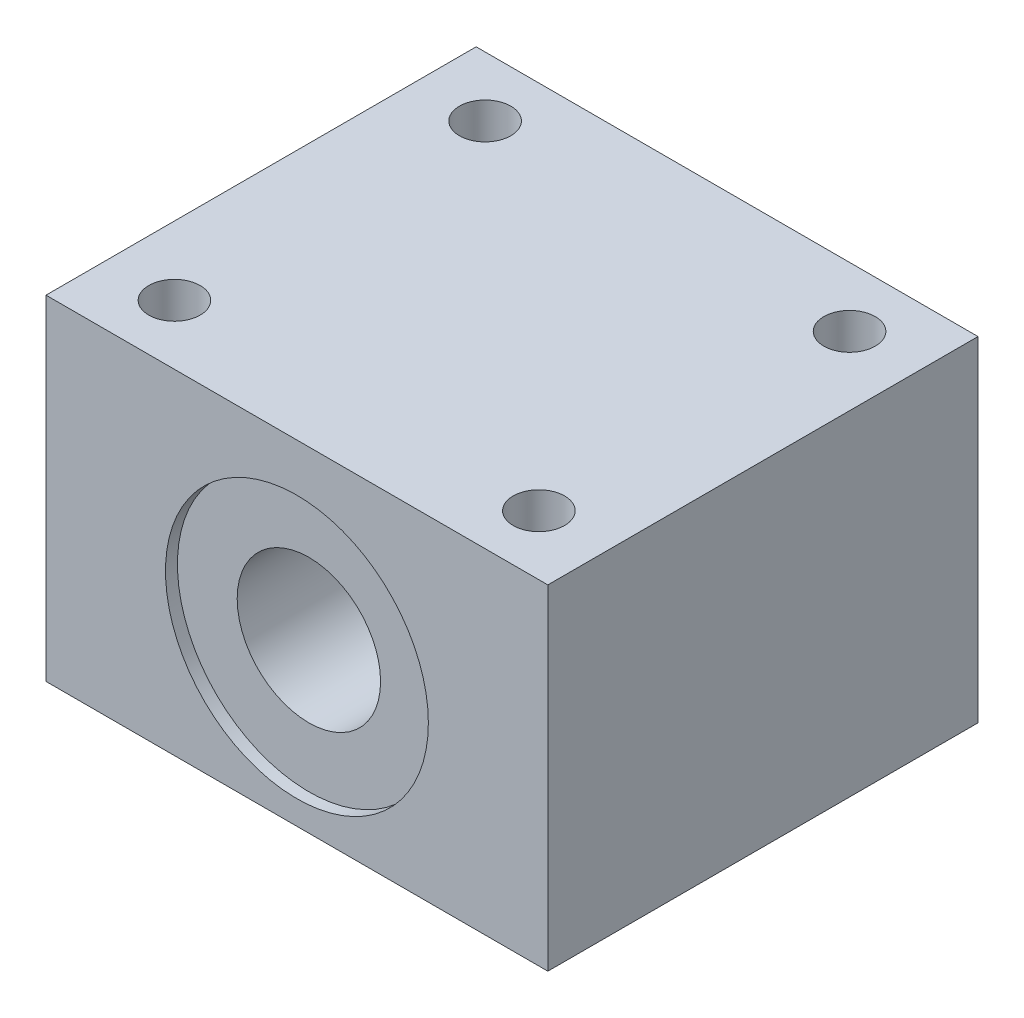
SolidWorks part; units mm, degrees
ref_plane "Front Plane" through (0, 0, 0) normal (0, 0, 1) x (1, 0, 0)
ref_plane "Top Plane" through (0, 0, 0) normal (0, 1, 0) x (1, 0, 0)
ref_plane "Right Plane" through (0, 0, 0) normal (1, 0, 0) x (0, 0, -1)
sketch "Sketch1" plane through (0, 0, 0) normal (0, 0, 1) x (1, 0, 0)
  line L1 (-21, -14) -> (21, -14)
  line L2 (-21, -14) -> (-21, 14)
  line L3 (-21, 14) -> (21, 14)
  line L4 (21, -14) -> (21, 14)
  line L5 (-21, -14) -> (21, 14) construction
  line L6 (-21, 14) -> (21, -14) construction
  circle A0 centre (0, -1) radius 6
  point P0 (0, 0)
  dimension "D3" = 12
  dimension "D1" = 42
  dimension "D2" = 28
  dimension "D4" = 21
  dimension "D5" = 15
extrude "Boss-Extrude1" add sketch "Sketch1" along normal mid plane 36
sketch "Sketch2" plane through (0, -14, 0) normal (0, -1, 0) x (-1, 0, 0)
  line L0 (0, -18) -> (0, 18) construction
  line L1 (21, -18) -> (-21, -18) construction
  line L2 (21, 18) -> (-21, 18) construction
  line L3 (21, 0) -> (-21, 0) construction
  line L4 (21, -18) -> (21, 18) construction
  line L5 (-21, -18) -> (-21, 18) construction
  circle A0 centre (15.25, -13) radius 2.15
  circle A1 centre (-15.25, -13) radius 2.15
  circle A2 centre (-15.25, 13) radius 2.15
  circle A3 centre (15.25, 13) radius 2.15
  dimension "D1" = 4.3
  dimension "D2" = 4.3
  dimension "D3" = 4.3
  dimension "D4" = 4.3
  dimension "D5" = 15.25
  dimension "D6" = 15.25
  dimension "D7" = 15.25
  dimension "D8" = 15.25
  dimension "D9" = 13
  dimension "D10" = 13
  dimension "D11" = 13
  dimension "D12" = 13
extrude "Cut-Extrude1" cut sketch "Sketch2" against normal through all
sketch "Sketch3" plane through (0, -14, 0) normal (0, -1, 0) x (1, 0, 0)
  circle A0 centre (-15.25, 13) radius 2.5
  circle A1 centre (15.25, 13) radius 2.5
  circle A2 centre (15.25, -13) radius 2.5
  circle A3 centre (-15.25, -13) radius 2.5
  dimension "D1" = 5
  dimension "D2" = 5
  dimension "D3" = 5
  dimension "D4" = 5
extrude "Cut-Extrude2" cut sketch "Sketch3" against normal blind 12
sketch "Sketch4" plane through (0, 0, 18) normal (0, 0, 1) x (1, 0, 0)
  circle A0 centre (0, -1) radius 11
  dimension "D1" = 22
extrude "Cut-Extrude3" cut sketch "Sketch4" against normal blind 1
sketch "Sketch5" plane through (0, 0, -18) normal (0, 0, -1) x (-1, 0, 0)
  circle A0 centre (0, -1) radius 11
  dimension "D1" = 22
extrude "Cut-Extrude4" cut sketch "Sketch5" against normal blind 1
